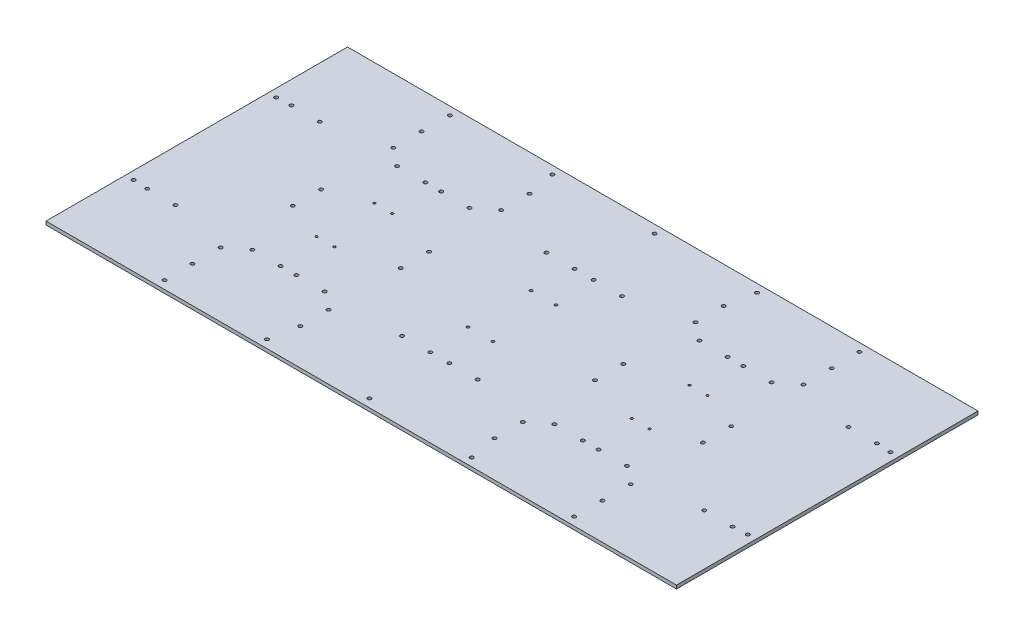
SolidWorks part; units mm, degrees
ref_plane "Front Plane" through (0, 0, 0) normal (0, 0, 1) x (1, 0, 0)
ref_plane "Top Plane" through (0, 0, 0) normal (0, 1, 0) x (1, 0, 0)
ref_plane "Right Plane" through (0, 0, 0) normal (1, 0, 0) x (0, 0, -1)
sketch "Sketch1" plane through (0, 0, 0) normal (0, 1, 0) x (1, 0, 0)
  line L0 (0, 139.7) -> (0, -139.7) construction
  line L1 (-292.1, 139.7) -> (292.1, 139.7)
  line L2 (-292.1, 139.7) -> (-292.1, -139.7)
  line L3 (-292.1, -139.7) -> (292.1, -139.7)
  line L4 (292.1, 139.7) -> (292.1, -139.7)
  line L5 (-292.1, 139.7) -> (292.1, -139.7) construction
  line L6 (-292.1, -139.7) -> (292.1, 139.7) construction
  line L7 (-284.6, 132.2) -> (284.6, 132.2) construction
  line L8 (-284.6, 132.2) -> (-284.6, -132.2) construction
  line L9 (-284.6, -132.2) -> (284.6, -132.2) construction
  line L10 (284.6, 132.2) -> (284.6, -132.2) construction
  line L11 (-284.6, 132.2) -> (284.6, -132.2) construction
  line L12 (-284.6, -132.2) -> (284.6, 132.2) construction
  line L13 (-292.1, 0) -> (292.1, 0) construction
  line L14 (284.6, 132.2) -> (284.6, -132.2) construction
  circle A0 centre (-284.6, 66.1) radius 1.65
  circle A1 centre (-189.7333, 132.2) radius 1.65
  circle A2 centre (-94.8667, 132.2) radius 1.65
  circle A3 centre (-284.6, -66.1) radius 1.65
  circle A4 centre (-94.8667, -132.2) radius 1.65
  circle A5 centre (-189.7333, -132.2) radius 1.65
  circle A6 centre (189.7333, -132.2) radius 1.65
  circle A7 centre (94.8667, -132.2) radius 1.65
  circle A8 centre (94.8667, 132.2) radius 1.65
  circle A9 centre (189.7333, 132.2) radius 1.65
  circle A10 centre (284.6, -66.1) radius 1.65
  circle A11 centre (284.6, 66.1) radius 1.65
  circle A12 centre (0, 132.2) radius 1.65
  circle A13 centre (0, -132.2) radius 1.65
  point P0 (0, 0)
  point P6 (0, 0)
  dimension "D5" = 3.3
  dimension "D6" = 3.3
  dimension "D7" = 3.3
  dimension "D12" = 3.3
  dimension "D13" = 3.3
  dimension "D1" = 584.2
  dimension "D2" = 279.4
  dimension "D3" = 7.5
  dimension "D4" = 7.5
  dimension "D8" = 66.1
  dimension "D9" = 94.8667
  dimension "D10" = 94.8667
  dimension "D11" = 94.8667
extrude "Boss-Extrude1" add sketch "Sketch1" along normal blind 3.175
sketch "Sketch2" plane through (0, 3.175, 0) normal (0, 1, 0) x (1, 0, 0)
  line L0 (0, 139.7) -> (0, -139.7) construction
  line L1 (292.1, 139.7) -> (-292.1, 139.7) construction
  line L2 (-292.1, -139.7) -> (292.1, -139.7) construction
  line L3 (-140, 139.7) -> (-140, -139.7) construction
  line L5 (-292.1, 0) -> (292.1, 0) construction
  line L6 (-292.1, 139.7) -> (-292.1, -139.7) construction
  line L7 (292.1, -139.7) -> (292.1, 139.7) construction
  line L8 (-190, 139.7) -> (-190, -139.7) construction
  circle A0 centre (-190, 13.1) radius 1.65
  circle A6 centre (-271.2, 66.8739) radius 1.65
  circle A7 centre (-245, 66.8739) radius 1.65
  circle A8 centre (-173.5, 67.0846) radius 1.65
  circle A9 centre (-147.3, 67.0846) radius 1.65
  circle A10 centre (-190, 106.2) radius 1.65
  circle A11 centre (-190, 80) radius 1.65
  circle A12 centre (-190, -80) radius 1.65
  circle A13 centre (-190, -106.2) radius 1.65
  circle A14 centre (-147.3, -67.0846) radius 1.65
  circle A15 centre (-173.5, -67.0846) radius 1.65
  circle A16 centre (-245, -66.8739) radius 1.65
  circle A17 centre (-271.2, -66.8739) radius 1.65
  circle A18 centre (-190, -13.1) radius 1.65
  circle A19 centre (-90, -13.1) radius 1.65
  circle A20 centre (-8.8, -66.8739) radius 1.65
  circle A21 centre (-35, -66.8739) radius 1.65
  circle A22 centre (-106.5, -67.0846) radius 1.65
  circle A23 centre (-132.7, -67.0846) radius 1.65
  circle A24 centre (-90, -106.2) radius 1.65
  circle A25 centre (-90, -80) radius 1.65
  circle A26 centre (-90, 80) radius 1.65
  circle A27 centre (-90, 106.2) radius 1.65
  circle A28 centre (-132.7, 67.0846) radius 1.65
  circle A29 centre (-106.5, 67.0846) radius 1.65
  circle A30 centre (-35, 66.8739) radius 1.65
  circle A31 centre (-8.8, 66.8739) radius 1.65
  circle A32 centre (-90, 13.1) radius 1.65
  circle A33 centre (90, 13.1) radius 1.65
  circle A34 centre (8.8, 66.8739) radius 1.65
  circle A35 centre (35, 66.8739) radius 1.65
  circle A36 centre (106.5, 67.0846) radius 1.65
  circle A37 centre (132.7, 67.0846) radius 1.65
  circle A38 centre (90, 106.2) radius 1.65
  circle A39 centre (90, 80) radius 1.65
  circle A40 centre (90, -80) radius 1.65
  circle A41 centre (90, -106.2) radius 1.65
  circle A42 centre (132.7, -67.0846) radius 1.65
  circle A43 centre (106.5, -67.0846) radius 1.65
  circle A44 centre (35, -66.8739) radius 1.65
  circle A45 centre (8.8, -66.8739) radius 1.65
  circle A46 centre (90, -13.1) radius 1.65
  circle A47 centre (190, -13.1) radius 1.65
  circle A48 centre (271.2, -66.8739) radius 1.65
  circle A49 centre (245, -66.8739) radius 1.65
  circle A50 centre (173.5, -67.0846) radius 1.65
  circle A51 centre (147.3, -67.0846) radius 1.65
  circle A52 centre (190, -106.2) radius 1.65
  circle A53 centre (190, -80) radius 1.65
  circle A54 centre (190, 80) radius 1.65
  circle A55 centre (190, 106.2) radius 1.65
  circle A56 centre (147.3, 67.0846) radius 1.65
  circle A57 centre (173.5, 67.0846) radius 1.65
  circle A58 centre (245, 66.8739) radius 1.65
  circle A59 centre (271.2, 66.8739) radius 1.65
  circle A60 centre (190, 13.1) radius 1.65
  point P72 (0, 0)
  dimension "D6" = 3.3
  dimension "D7" = 3.3
  dimension "D12" = 3.3
  dimension "D13" = 3.3
  dimension "D2" = 3.3
  dimension "D8" = 3.3
  dimension "D9" = 3.3
  dimension "D4" = 13.1
  dimension "D10" = 26.2
  dimension "D11" = 26.2
  dimension "D14" = 26.2
  dimension "D5" = 0
  dimension "D15" = 16.5
  dimension "D3" = 190
  dimension "D16" = 55
  dimension "D17" = 80
  dimension "D18" = 50
extrude "Cut-Extrude1" cut sketch "Sketch2" against normal up to surface (3.175 mm away) up to face at (0, 0, 0)
sketch "Sketch3" plane through (0, 3.175, 0) normal (0, 1, 0) x (1, 0, 0)
  line L1 (-11.525, 29.25) -> (11.525, 29.25) construction
  line L2 (-11.525, 29.25) -> (-11.525, -29.25) construction
  line L3 (-11.525, -29.25) -> (11.525, -29.25) construction
  line L4 (11.525, 29.25) -> (11.525, -29.25) construction
  line L5 (-11.525, 29.25) -> (11.525, -29.25) construction
  line L6 (-11.525, -29.25) -> (11.525, 29.25) construction
  line L7 (-146.05, 139.7) -> (-146.05, -139.7) construction
  line L8 (292.1, 139.7) -> (-292.1, 139.7) construction
  line L9 (-292.1, -139.7) -> (292.1, -139.7) construction
  line L10 (0, 139.7) -> (0, -139.7) construction
  line L11 (-292.1, 139.7) -> (-292.1, -139.7) construction
  line L12 (154.3, -26.75) -> (137.8, 26.75) construction
  line L13 (-154.3, 26.75) -> (-137.8, 26.75) construction
  line L14 (-154.3, 26.75) -> (-154.3, -26.75) construction
  line L15 (-154.3, -26.75) -> (-137.8, -26.75) construction
  line L16 (-137.8, 26.75) -> (-137.8, -26.75) construction
  line L17 (-154.3, 26.75) -> (-137.8, -26.75) construction
  line L18 (-154.3, -26.75) -> (-137.8, 26.75) construction
  line L19 (154.3, 26.75) -> (137.8, -26.75) construction
  line L20 (137.8, 26.75) -> (137.8, -26.75) construction
  line L21 (154.3, -26.75) -> (137.8, -26.75) construction
  line L22 (154.3, 26.75) -> (154.3, -26.75) construction
  line L23 (154.3, 26.75) -> (137.8, 26.75) construction
  line L24 (146.05, 139.7) -> (146.05, -139.7) construction
  circle A0 centre (-11.525, 29.25) radius 1.3
  circle A1 centre (11.525, 29.25) radius 1.3
  circle A2 centre (11.525, -29.25) radius 1.3
  circle A3 centre (-11.525, -29.25) radius 1.3
  circle A4 centre (-154.3, 26.75) radius 1.1
  circle A5 centre (-137.8, 26.75) radius 1.1
  circle A6 centre (-137.8, -26.75) radius 1.1
  circle A7 centre (-154.3, -26.75) radius 1.1
  circle A8 centre (154.3, -26.75) radius 1.1
  circle A9 centre (137.8, -26.75) radius 1.1
  circle A10 centre (137.8, 26.75) radius 1.1
  circle A11 centre (154.3, 26.75) radius 1.1
  point P0 (0, 0)
  point P20 (-146.05, 0)
  point P39 (146.05, 0)
  dimension "D1" = 2.6
  dimension "D6" = 2.2
  dimension "D2" = 58.5
  dimension "D3" = 23.05
  dimension "D4" = 292.1
  dimension "D5" = 146.05
  dimension "D7" = 53.5
  dimension "D8" = 16.5
extrude "Cut-Extrude2" cut sketch "Sketch3" against normal up to surface (3.175 mm away) up to face at (-106.5, 0, 68.7346)
equation "\"D6@Sketch1\"=\"D5@Sketch1\""
equation "\"D7@Sketch1\"=\"D5@Sketch1\""
equation "\"D10@Sketch1\"=\"D9@Sketch1\""
equation "\"D12@Sketch1\"=\"D5@Sketch1\""
equation "\"D13@Sketch1\"=\"D5@Sketch1\""
equation "\"D6@Sketch2\"=\"D2@Sketch2\""
equation "\"D7@Sketch2\"=\"D2@Sketch2\""
equation "\"D8@Sketch2\"=\"D2@Sketch2\""
equation "\"D9@Sketch2\"=\"D2@Sketch2\""
equation "\"D11@Sketch2\"=\"D10@Sketch2\""
equation "\"D4@Sketch2\"=\"D10@Sketch2\"/2"
equation "\"D12@Sketch2\"=\"D6@Sketch2\""
equation "\"D13@Sketch2\"=\"D6@Sketch2\""
equation "\"D14@Sketch2\"=\"D10@Sketch2\""
equation "\"D5@Sketch3\"=\"D4@Sketch3\"/2"
